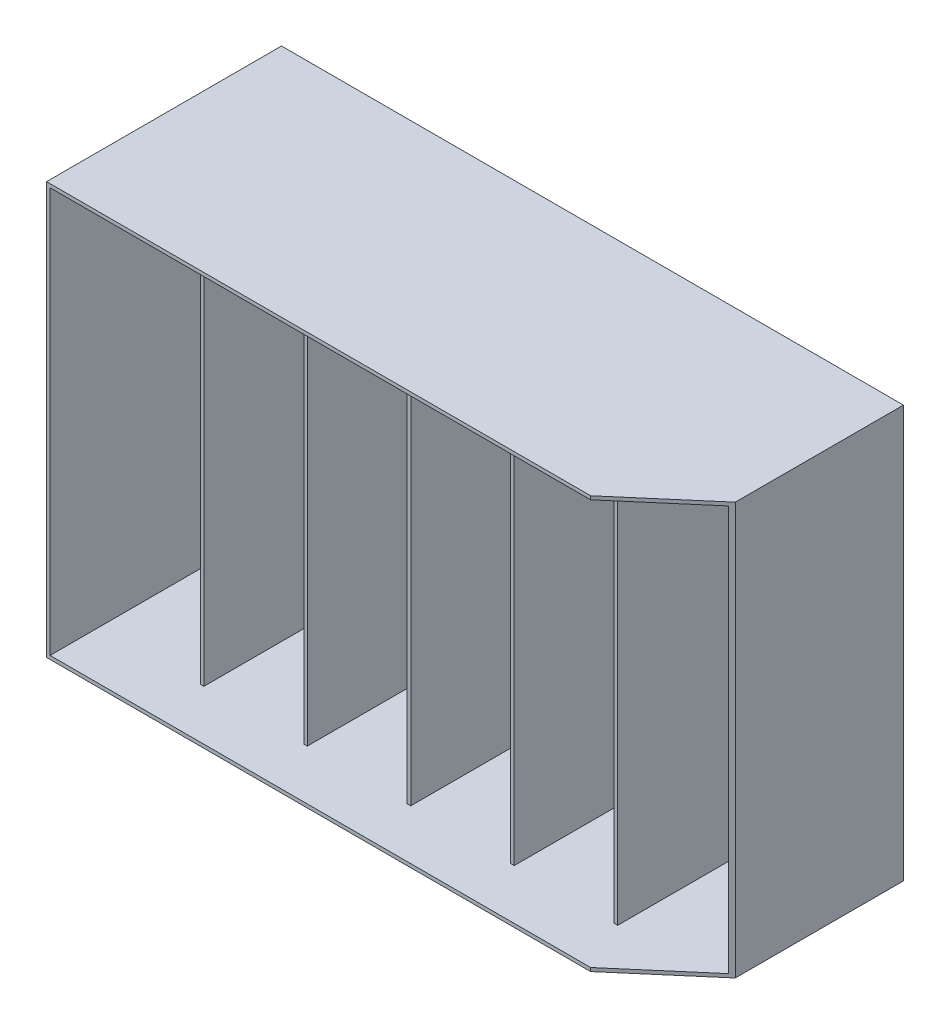
SolidWorks part; units mm, degrees
material "Custom Plastic"
ref_plane "X-Y Datum" through (0, 0, 0) normal (0, 0, 1) x (1, 0, 0)
ref_plane "X-Z Datum" through (0, 0, 0) normal (0, 1, 0) x (1, 0, 0)
ref_plane "Y-Z Datum" through (0, 0, 0) normal (1, 0, 0) x (0, 0, -1)
sketch "Sketch1" plane through (0, 0, 0) normal (0, 0, 1) x (1, 0, 0)
  line L0 (-276.225, 0) -> (276.225, 0) construction
  line L1 (-276.225, 181.95) -> (276.225, 181.95)
  line L2 (-276.225, 181.95) -> (-276.225, -181.95)
  line L3 (-276.225, -181.95) -> (276.225, -181.95)
  line L4 (276.225, 181.95) -> (276.225, -181.95)
  line L5 (-276.225, 181.95) -> (276.225, -181.95) construction
  line L6 (-276.225, -181.95) -> (276.225, 181.95) construction
  line L7 (-273.05, 178.775) -> (-189.45, 178.775) construction
  line L8 (-273.05, 178.775) -> (-273.05, -178.775) construction
  line L9 (-273.05, -178.775) -> (-189.45, -178.775) construction
  line L10 (-189.45, 178.775) -> (-189.45, -178.775) construction
  line L11 (-273.05, 178.775) -> (-189.45, -178.775) construction
  line L12 (-273.05, -178.775) -> (-189.45, 178.775) construction
  line L13 (-186.275, -181.95) -> (-186.275, 181.95)
  line L14 (-279.4, 185.125) -> (279.4, 185.125)
  line L15 (279.4, 185.125) -> (279.4, -185.125)
  line L16 (-279.4, -185.125) -> (279.4, -185.125)
  line L17 (-279.4, 185.125) -> (-279.4, -185.125)
  line L18 (-183.1, -181.95) -> (-183.1, 181.95)
  line L19 (-186.275, 0) -> (-183.1, 0) construction
  line L20 (-180.086, 178.775) -> (-180.086, -178.775) construction
  line L21 (-180.086, 178.775) -> (-96.486, 178.775) construction
  line L22 (-96.486, 178.775) -> (-96.486, -178.775) construction
  line L23 (-180.086, -178.775) -> (-96.486, -178.775) construction
  line L24 (-93.311, -181.95) -> (-93.311, 181.95)
  line L25 (-90.136, -181.95) -> (-90.136, 181.95)
  line L26 (-87.122, 178.775) -> (-87.122, -178.775) construction
  line L27 (-87.122, 178.775) -> (-3.522, 178.775) construction
  line L28 (-3.522, 178.775) -> (-3.522, -178.775) construction
  line L29 (-87.122, -178.775) -> (-3.522, -178.775) construction
  line L30 (-0.347, -181.95) -> (-0.347, 181.95)
  line L31 (2.828, -181.95) -> (2.828, 181.95)
  line L32 (5.842, 178.775) -> (5.842, -178.775) construction
  line L33 (5.842, 178.775) -> (89.442, 178.775) construction
  line L34 (89.442, 178.775) -> (89.442, -178.775) construction
  line L35 (5.842, -178.775) -> (89.442, -178.775) construction
  line L36 (92.617, -181.95) -> (92.617, 181.95)
  line L37 (95.792, -181.95) -> (95.792, 181.95)
  line L38 (98.806, 178.775) -> (98.806, -178.775) construction
  line L39 (98.806, 178.775) -> (182.406, 178.775) construction
  line L40 (182.406, 178.775) -> (182.406, -178.775) construction
  line L41 (98.806, -178.775) -> (182.406, -178.775) construction
  line L42 (185.581, -181.95) -> (185.581, 181.95)
  line L43 (188.756, -181.95) -> (188.756, 181.95)
  line L44 (-180.086, -178.775) -> (-96.486, 178.775) construction
  line L45 (-180.086, 178.775) -> (-96.486, -178.775) construction
  line L46 (-87.122, -178.775) -> (-3.522, 178.775) construction
  line L47 (-87.122, 178.775) -> (-3.522, -178.775) construction
  line L48 (5.842, -178.775) -> (89.442, 178.775) construction
  line L49 (5.842, 178.775) -> (89.442, -178.775) construction
  line L50 (98.806, -178.775) -> (182.406, 178.775) construction
  line L51 (98.806, 178.775) -> (182.406, -178.775) construction
  point P0 (0, 0)
  point P6 (-231.25, 0)
  point P23 (-184.6875, 0)
  point P24 (-138.286, 0)
  dimension "D1" = 357.55
  dimension "D2" = 83.6
  dimension "D3" = 3.175
  dimension "D4" = 3.175
  dimension "D5" = 3.175
  dimension "D8" = 46.5625
  dimension "D10" = 558.8
  dimension "D12" = 92.964
  dimension "D6" = 3.175
  dimension "D7" = 3.175
  dimension "D9" = 5
  dimension "D11" = 5
extrude "Boss-Extrude1" add sketch "Sketch1" along normal blind 3.175 contours L3 L13 L1 L2 | L3 L24 L1 L18 | L3 L18 L1 L13 | L14 L17 L16 L15 L1 L4 L3 L2 | L3 L30 L1 L25 | L3 L25 L1 L24 | L3 L36 L1 L31 | L3 L31 L1 L30 | L3 L42 L1 L37 | L3 L37 L1 L36 | L43 L3 L4 L1 | L3 L43 L1 L42 region at (-231.25, 0, 0) region at (-184.6875, 0, 0) region at (-138.2055, 0, 0) region at (-91.7235, 0, 0) region at (-45.2415, 0, 0) region at (1.2405, 0, 0) region at (47.7225, 0, 0) region at (94.2045, 0, 0) region at (140.6865, 0, 0) region at (187.1685, 0, 0) region at (232.4905, 0, 0) region at (0, 184.4547, 0)
sketch "Sketch2" plane through (0, 0, 3.175) normal (0, 0, 1) x (1, 0, 0)
  line L0 (-186.275, -181.95) -> (-186.275, 181.95) construction
  line L1 (-93.311, -181.95) -> (-93.311, 181.95) construction
  line L2 (-183.1, -181.95) -> (-183.1, 181.95) construction
  line L3 (92.617, -181.95) -> (92.617, 181.95) construction
  line L4 (276.225, 181.95) -> (-276.225, 181.95)
  line L5 (276.225, -181.95) -> (276.225, 181.95)
  line L6 (-276.225, -181.95) -> (276.225, -181.95)
  line L7 (-276.225, 181.95) -> (-276.225, -181.95)
  line L8 (276.225, 181.95) -> (-276.225, 181.95)
  line L9 (276.225, -181.95) -> (276.225, 181.95)
  line L10 (-276.225, -181.95) -> (276.225, -181.95)
  line L11 (-276.225, 181.95) -> (-276.225, -181.95)
  line L12 (-279.4, -185.125) -> (279.4, -185.125)
  line L13 (-279.4, 185.125) -> (-279.4, -185.125)
  line L14 (279.4, 185.125) -> (-279.4, 185.125)
  line L15 (279.4, -185.125) -> (279.4, 185.125)
  line L16 (-279.4, -185.125) -> (279.4, -185.125)
  line L17 (-279.4, 185.125) -> (-279.4, -185.125)
  line L18 (279.4, 185.125) -> (-279.4, 185.125)
  line L19 (279.4, -185.125) -> (279.4, 185.125)
  line L20 (2.828, -181.95) -> (2.828, 181.95) construction
  line L21 (-0.347, -181.95) -> (-0.347, 181.95) construction
  line L22 (-90.136, -181.95) -> (-90.136, 181.95) construction
  line L23 (188.756, -181.95) -> (188.756, 181.95) construction
  line L24 (185.581, -181.95) -> (185.581, 181.95) construction
  line L25 (95.792, -181.95) -> (95.792, 181.95) construction
  line L26 (-186.275, -181.95) -> (-186.275, 181.95)
  line L27 (-93.311, -181.95) -> (-93.311, 181.95)
  line L28 (-183.1, -181.95) -> (-183.1, 181.95)
  line L29 (92.617, -181.95) -> (92.617, 181.95)
  line L30 (2.828, -181.95) -> (2.828, 181.95)
  line L31 (-0.347, -181.95) -> (-0.347, 181.95)
  line L32 (-90.136, -181.95) -> (-90.136, 181.95)
  line L33 (188.756, -181.95) -> (188.756, 181.95)
  line L34 (185.581, -181.95) -> (185.581, 181.95)
  line L35 (95.792, -181.95) -> (95.792, 181.95)
  line M9 (279.4, 185.125) -> (-279.4, 185.125)
  line M10 (-279.4, 185.125) -> (-279.4, -185.125)
  line M11 (-279.4, -185.125) -> (279.4, -185.125)
  line M12 (279.4, -185.125) -> (279.4, 185.125)
  dimension "D1" = 0
  dimension "D2" = 0
extrude "Boss-Extrude2" add sketch "Sketch2" along normal blind 162.9 contours L11 L8 L9 L10 M12 M9 M10 M11 | L10 L28 L8 L26 | L10 L32 L8 L27 | L31 L10 L30 L8 | L10 L35 L8 L29 | L34 L10 L33 L8 region at (187.1685, 0, 3.175) region at (94.2045, 0, 3.175) region at (1.2405, 0, 3.175) region at (-91.7235, 0, 3.175) region at (-184.6875, 0, 3.175) region at (-278.7297, 0, 3.175)
sketch "Sketch3" plane through (0, 0, 166.075) normal (0, 0, 1) x (1, 0, 0)
  line L0 (-186.275, -181.95) -> (-186.275, 181.95) construction
  line L1 (-93.311, -181.95) -> (-93.311, 181.95) construction
  line L2 (-183.1, -181.95) -> (-183.1, 181.95) construction
  line L3 (92.617, -181.95) -> (92.617, 181.95) construction
  line L4 (276.225, 181.95) -> (-276.225, 181.95)
  line L5 (276.225, -181.95) -> (276.225, 181.95)
  line L6 (-276.225, -181.95) -> (276.225, -181.95)
  line L7 (-276.225, 181.95) -> (-276.225, -181.95)
  line L8 (276.225, 181.95) -> (-276.225, 181.95)
  line L9 (276.225, -181.95) -> (276.225, 181.95)
  line L10 (-276.225, -181.95) -> (276.225, -181.95)
  line L11 (-276.225, 181.95) -> (-276.225, -181.95)
  line L12 (-279.4, -185.125) -> (279.4, -185.125)
  line L13 (-279.4, 185.125) -> (-279.4, -185.125)
  line L14 (279.4, 185.125) -> (-279.4, 185.125)
  line L15 (279.4, -185.125) -> (279.4, 185.125)
  line L16 (-279.4, -185.125) -> (279.4, -185.125)
  line L17 (-279.4, 185.125) -> (-279.4, -185.125)
  line L18 (279.4, 185.125) -> (-279.4, 185.125)
  line L19 (279.4, -185.125) -> (279.4, 185.125)
  line L20 (2.828, -181.95) -> (2.828, 181.95) construction
  line L21 (-0.347, -181.95) -> (-0.347, 181.95) construction
  line L22 (-90.136, -181.95) -> (-90.136, 181.95) construction
  line L23 (188.756, -181.95) -> (188.756, 181.95) construction
  line L24 (185.581, -181.95) -> (185.581, 181.95) construction
  line L25 (95.792, -181.95) -> (95.792, 181.95) construction
  line L26 (-186.275, -181.95) -> (-186.275, 181.95)
  line L27 (-93.311, -181.95) -> (-93.311, 181.95)
  line L28 (-183.1, -181.95) -> (-183.1, 181.95)
  line L29 (92.617, -181.95) -> (92.617, 181.95)
  line L30 (2.828, -181.95) -> (2.828, 181.95)
  line L31 (-0.347, -181.95) -> (-0.347, 181.95)
  line L32 (-90.136, -181.95) -> (-90.136, 181.95)
  line L33 (188.756, -181.95) -> (188.756, 181.95)
  line L34 (185.581, -181.95) -> (185.581, 181.95)
  line L35 (95.792, -181.95) -> (95.792, 181.95)
  line M9 (95.792, 181.95) -> (185.581, 181.95)
  line M11 (185.581, -181.95) -> (95.792, -181.95)
  line M13 (2.828, 181.95) -> (92.617, 181.95)
  line M15 (92.617, -181.95) -> (2.828, -181.95)
  line M17 (-90.136, 181.95) -> (-0.347, 181.95)
  line M19 (-0.347, -181.95) -> (-90.136, -181.95)
  line M21 (-183.1, 181.95) -> (-93.311, 181.95)
  line M23 (-93.311, -181.95) -> (-183.1, -181.95)
  line M25 (-276.225, 181.95) -> (-186.275, 181.95)
  line M27 (-186.275, -181.95) -> (-276.225, -181.95)
  line M28 (-276.225, -181.95) -> (-276.225, 181.95)
  line M30 (188.756, 181.95) -> (276.225, 181.95)
  line M31 (276.225, 181.95) -> (276.225, -181.95)
  line M32 (276.225, -181.95) -> (188.756, -181.95)
  line M33 (279.4, -185.125) -> (279.4, 185.125)
  line M34 (279.4, 185.125) -> (-279.4, 185.125)
  line M35 (-279.4, 185.125) -> (-279.4, -185.125)
  line M36 (-279.4, -185.125) -> (279.4, -185.125)
  dimension "D1" = 0
  dimension "D2" = 0
extrude "Boss-Extrude3" add sketch "Sketch3" along normal blind 45 contours L10 L8 M36 M33 M34 M35 M27 M28 M25 M21 M17 M13 M9 M30 M31 M32 M11 M15 M19 M23 region at (-278.7297, 0, 166.075)
sketch "Sketch4" plane through (0, -185.125, 0) normal (0, -1, 0) x (1, 0, 0)
  line L0 (209.4, 211.075) -> (279.4, 151.075)
  line L1 (-279.4, 211.075) -> (279.4, 211.075) construction
  line L2 (279.4, 211.075) -> (279.4, 0) construction
  line M3 (279.4, 0) -> (279.4, 211.075)
  line M4 (279.4, 211.075) -> (-279.4, 211.075)
  dimension "D1" = 60
  dimension "D2" = 70
extrude "Cut-Extrude1" cut sketch "Sketch4" against normal through all contours L0 M4 M3 region at (256.0667, -185.125, 191.075)
